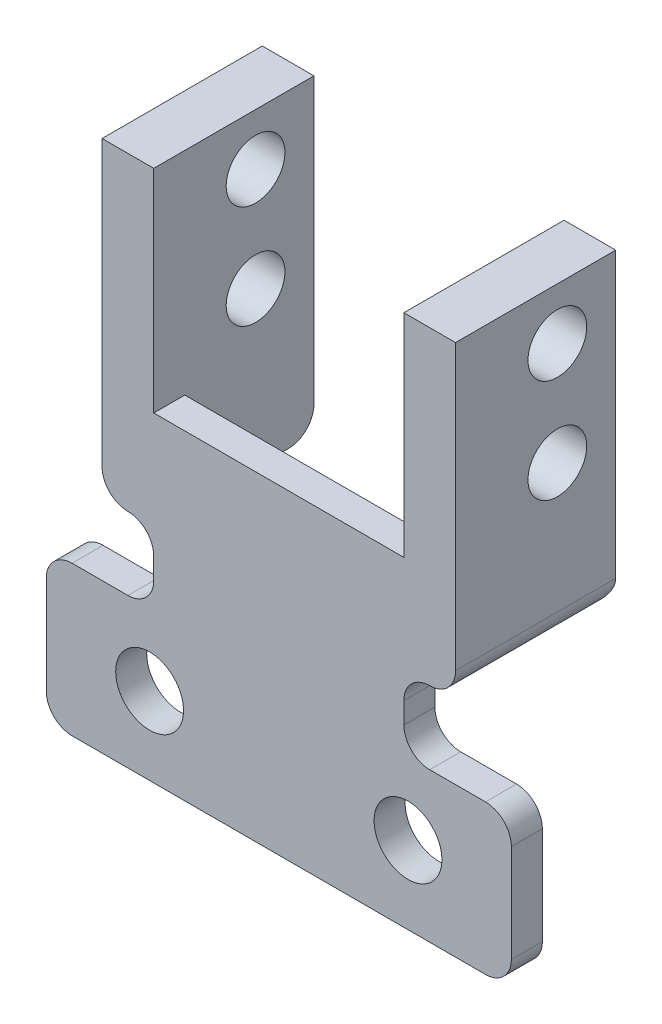
SolidWorks part; units mm, degrees
ref_plane "Front Plane" through (0, 0, 0) normal (0, 0, 1) x (1, 0, 0)
ref_plane "Top Plane" through (0, 0, 0) normal (0, 1, 0) x (1, 0, 0)
ref_plane "Right Plane" through (0, 0, 0) normal (1, 0, 0) x (0, 0, -1)
sketch "Sketch1" plane through (0, 0, 0) normal (0, 0, 1) x (1, 0, 0)
  line L1 (-8.5113, 5.428) -> (36.4887, 5.428)
  line L2 (-8.5113, 5.428) -> (-8.5113, -9.032)
  line L3 (-8.5113, -9.032) -> (36.4887, -9.032)
  line L4 (36.4887, 5.428) -> (36.4887, -9.032)
  dimension "D1" = 45
  dimension "D2" = 14.46
extrude "Boss-Extrude1" add sketch "Sketch1" along normal blind 3
sketch "Sketch2" plane through (0, 0, 0) normal (0, 0, -1) x (-1, 0, 0)
  line L0 (8.5113, -9.032) -> (-36.4887, -9.032) construction
  line L1 (-36.4887, 5.428) -> (8.5113, 5.428) construction
  point P0 (-26.4887, -1.532)
  point P1 (-1.4887, -1.532)
  point P4 (-13.9887, -9.032)
  dimension "D1" = 25
  dimension "D2" = 12.5
  dimension "D3" = 6.96
hole_wizard "1/4 (0.2584625) Diameter Hole1" positions "Sketch3" profile "Sketch4" hole size "1/4" standard "ANSI Inch" end condition through all
sketch "Sketch3" plane through (0, 0, 0) normal (0, 0, -1) x (-1, 0, 0)
  point P0 (-26.4887, -1.532)
  point P3 (-1.4887, -1.532)
sketch "Sketch4" plane through (26.4887, -1.532, 0) normal (1, 0, 0) x (0, 1, 0)
  line L0 (0, 0) -> (0, 3)
  line L1 (0, 3) -> (3.2825, 3)
  line L2 (3.2825, 3) -> (3.2825, 0)
  line L5 (3.2825, 0) -> (0, 0)
  line L11 (0, -6.35) -> (0, 107.95) construction
  dimension "Thru Hole Dia." = 6.5649
  dimension "Thru Hole Depth" = 3
sketch "Sketch5" plane through (0, 0, 0) normal (0, 0, -1) x (-1, 0, 0)
  line L0 (-36.4887, 5.428) -> (8.5113, 5.428) construction
  line L1 (-26.0887, 5.428) -> (-1.8887, 5.428)
  line L2 (-26.0887, 5.428) -> (-26.0887, 42.468)
  line L3 (-26.0887, 42.468) -> (-1.8887, 42.468)
  line L4 (-1.8887, 5.428) -> (-1.8887, 42.468)
  line L5 (8.5113, -9.032) -> (-36.4887, -9.032) construction
  point P6 (-13.9887, 42.468)
  point P9 (-13.9887, -9.032)
  dimension "D1" = 24.2
  dimension "D2" = 0
  dimension "D3" = 44
extrude "Boss-Extrude2" add sketch "Sketch5" against normal blind 3
sketch "Sketch6" plane through (1.8887, 0, 0) normal (-1, 0, 0) x (0, 0, 1)
  line L0 (0, 5.428) -> (0, 42.468) construction
  line L1 (3, 42.468) -> (-12.5, 42.468)
  line L2 (3, 42.468) -> (3, 12.468)
  line L3 (3, 12.468) -> (-12.5, 12.468)
  line L4 (-12.5, 42.468) -> (-12.5, 12.468)
  dimension "D1" = 30
  dimension "D2" = 12.5
extrude "Boss-Extrude3" add sketch "Sketch6" along normal blind 5
sketch "Sketch7" plane through (-3.1113, 0, 0) normal (-1, 0, 0) x (0, 0, 1)
  line L1 (-12.5, 42.468) -> (3, 42.468)
  line L2 (-12.5, 42.468) -> (-12.5, 12.468)
  line L3 (-12.5, 12.468) -> (3, 12.468)
  line L4 (3, 42.468) -> (3, 12.468)
extrude "Boss-Extrude4" add sketch "Sketch7" against normal blind 5 from surface starting at face at (26.0887, 23.948, 1.5)
sketch "Sketch8" plane through (-3.1113, 0, 0) normal (-1, 0, 0) x (0, 0, 1)
  line L2 (3, 42.468) -> (-12.5, 42.468) construction
  line L3 (3, 12.468) -> (3, 42.468) construction
  point P0 (-6.85, 27.468)
  point P1 (-6.85, 37.468)
  dimension "D1" = 9.85
  dimension "D2" = 0
  dimension "D3" = 5
  dimension "D4" = 10
sketch "Sketch12" plane through (0, 0, 0) normal (0, 0, -1) x (-1, 0, 0)
  line L0 (-1.8887, 12.468) -> (-1.8887, 42.468) construction
  line L1 (-26.0887, 42.468) -> (-1.8887, 42.468)
  line L2 (-26.0887, 42.468) -> (-26.0887, 21.968)
  line L3 (-26.0887, 21.968) -> (-1.8887, 21.968)
  line L4 (-1.8887, 42.468) -> (-1.8887, 21.968)
  dimension "D1" = 20.5
extrude "Cut-Extrude1" cut sketch "Sketch12" against normal up to surface (3 mm away) up to face at (23.2062, -1.532, 3)
hole_wizard "M5 Clearance Hole1" positions "Sketch9" profile "Sketch10" hole size "M5" standard "ANSI Metric" end condition through all
sketch "Sketch9" plane through (-3.1113, 0, 0) normal (-1, 0, 0) x (0, 0, 1)
  point P0 (-6.85, 37.468)
  point P3 (-6.85, 27.468)
sketch "Sketch10" plane through (-3.1113, 37.468, -6.85) normal (0, 1, 0) x (0, 0, 1)
  line L0 (0, 0) -> (0, 39.6)
  line L1 (0, 39.6) -> (2.8431, 39.6)
  line L2 (2.8431, 39.6) -> (2.8431, 0)
  line L5 (2.8431, 0) -> (0, 0)
  line L11 (0, -6.35) -> (0, 107.95) construction
  dimension "Thru Hole Dia." = 5.6862
  dimension "Thru Hole Depth" = 39.6
fillet "Fillet3" radius 2.5 4 edges at (36.4887, -9.032, 1.5) (36.4887, 5.428, 1.5) (-8.5113, -9.032, 1.5) (-8.5113, 5.428, 1.5)
fillet "Fillet4" radius 2.5 8 edges at (1.8887, 5.428, 1.5) (26.0887, 5.428, 1.5) (26.0887, 12.468, 1.5) (1.8887, 12.468, 1.5) (31.0887, 12.468, -4.75) (-3.1113, 12.468, -4.75) (28.5887, 12.468, -12.5) (-0.6113, 12.468, -12.5)
equation "\"D3@Sketch5\"=15+20 + 9"
